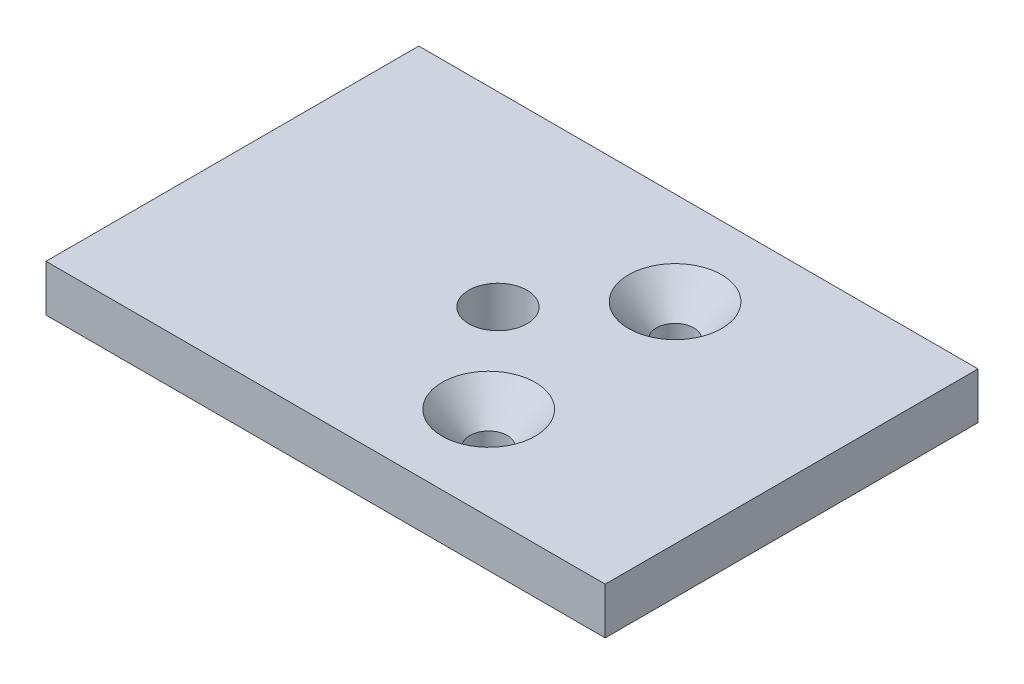
SolidWorks part; units mm, degrees
material "6061 Alloy"
ref_plane "Front Plane" through (0, 0, 0) normal (0, 0, 1) x (1, 0, 0)
ref_plane "Top Plane" through (0, 0, 0) normal (0, 1, 0) x (1, 0, 0)
ref_plane "Right Plane" through (0, 0, 0) normal (1, 0, 0) x (0, 0, -1)
sketch "Sketch1" plane through (0, 0, 0) normal (0, 1, 0) x (1, 0, 0)
  line L1 (0, 0) -> (76.2, 0)
  line L2 (0, 0) -> (0, 50.8)
  line L3 (0, 50.8) -> (76.2, 50.8)
  line L4 (76.2, 0) -> (76.2, 50.8)
  dimension "D1" = 50.8
  dimension "D2" = 76.2
extrude "Boss-Extrude1" add sketch "Sketch1" along normal blind 6.35
hole_wizard "1/4-20 Tapped Hole1" positions "Sketch2" profile "Sketch3" tap size "1/4-20" standard "ANSI Inch" end condition through all
sketch "Sketch2" plane through (0, 6.35, 0) normal (0, 1, 0) x (1, 0, 0)
  line L8 (0, 0) -> (76.2, 0) construction
  line L9 (76.2, 50.8) -> (0, 50.8) construction
  line L10 (47.625, 0) -> (47.625, 12.7) construction
  line L11 (47.625, 12.7) -> (47.625, 38.1) construction
  line L12 (47.625, 38.1) -> (47.625, 50.8) construction
  line L14 (76.2, 0) -> (76.2, 50.8) construction
  point P0 (47.625, 12.7)
  point P2 (47.625, 38.1)
  point P35 (0, 0)
  point P36 (0, 0)
  dimension "D1" = 12.7
  dimension "D2" = 12.7
  dimension "D3" = 28.575
sketch "Sketch3" plane through (47.625, 6.35, -12.7) normal (1, 0, 0) x (0, 0, 1)
  line L0 (0, 0) -> (0, 6.35)
  line L1 (0, 6.35) -> (2.5527, 6.35)
  line L2 (2.5527, 6.35) -> (2.5527, 4.3683)
  line L3 (2.5527, 4.3683) -> (6.35, 0)
  line L5 (6.35, 0) -> (0, 0)
  line L6 (-2.5527, 4.3683) -> (-6.35, 0) construction
  line L11 (0, -6.35) -> (0, 107.95) construction
  dimension "Thru Tap Drill Dia." = 5.1054
  dimension "Thru Tap Drill Depth" = 6.35
  dimension "Near C'Sink Dia." = 12.7
  dimension "Near C'Sink Angle" = 82
cosmetic thread "Hole Thread1" parameters "D2"=6.35
cosmetic thread "Hole Thread2" parameters "D2"=6.35
hole_wizard "3/8-16 Tapped Hole1" positions "Sketch6" profile "Sketch7" tap size "3/8-16" standard "ANSI Inch" end condition up to next
sketch "Sketch6" plane through (0, 6.35, 0) normal (0, 1, 0) x (1, 0, 0)
  line L0 (0, 25.4) -> (76.2, 25.4) construction
  line L1 (0, 50.8) -> (0, 0) construction
  line L2 (76.2, 0) -> (76.2, 50.8) construction
  point P0 (36.1829, 25.4)
  point P9 (0, 0)
  point P10 (24.8899, 24.6656)
  point P11 (36.1829, 25.4)
sketch "Sketch7" plane through (36.1829, 6.35, -25.4) normal (1, 0, 0) x (0, 0, 1)
  line L0 (0, 0) -> (0, 6.35)
  line L1 (0, 6.35) -> (3.9687, 6.35)
  line L2 (3.9687, 6.35) -> (3.9687, 0)
  line L5 (3.9687, 0) -> (0, 0)
  line L11 (0, -6.35) -> (0, 107.95) construction
  dimension "Thru Tap Drill Dia." = 7.9375
  dimension "Thru Tap Drill Depth" = 6.35
cosmetic thread "Hole Thread3" parameters "D2"=9.525
